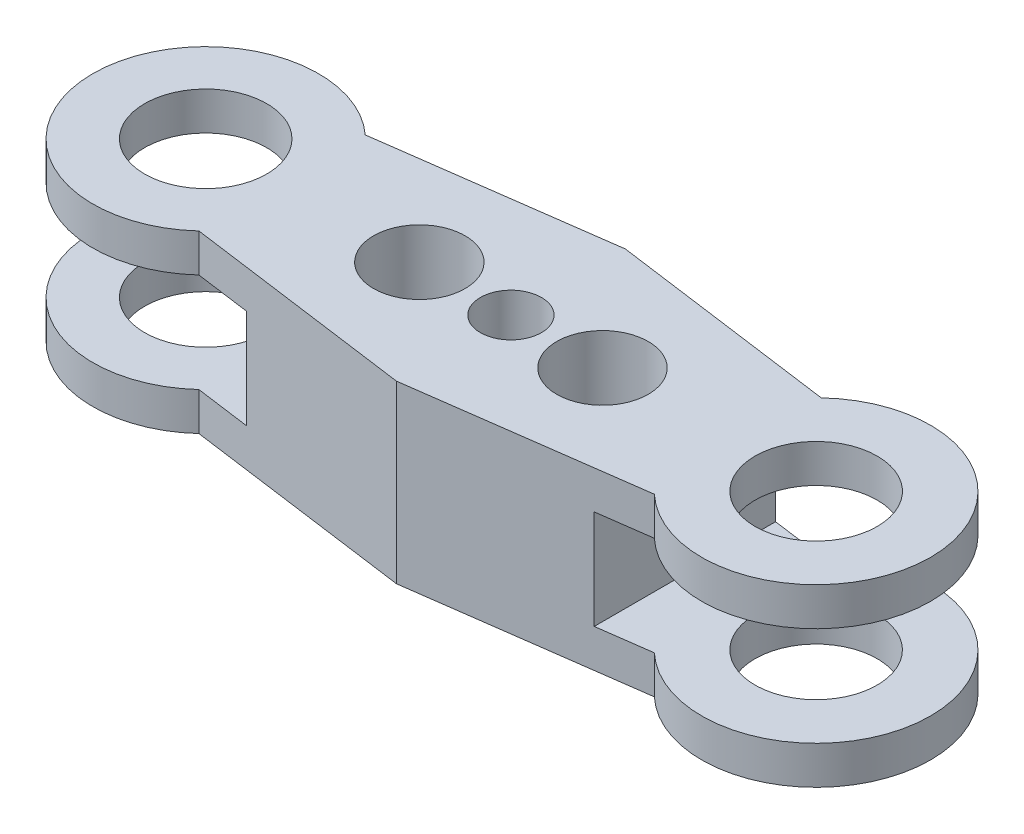
SolidWorks part; units mm, degrees
ref_plane "Ön Düzlem" through (0, 0, 0) normal (0, 0, 1) x (1, 0, 0)
ref_plane "Üst Düzlem" through (0, 0, 0) normal (0, 1, 0) x (1, 0, 0)
ref_plane "Sağ Düzlem" through (0, 0, 0) normal (1, 0, 0) x (0, 0, -1)
sketch "Çizim2" plane through (0, 0, 0) normal (0, 1, 0) x (1, 0, 0)
  line L0 (14.8663, -5.4676) -> (14.9951, -5.45)
  line L3 (14.8663, 5.4676) -> (14.9951, 5.45)
  line L4 (-14.9951, 5.45) -> (0, 7.5)
  line L5 (-14.9951, -5.45) -> (0, -7.5)
  line L6 (14.9951, 5.45) -> (0, 7.5)
  line L7 (14.9951, -5.45) -> (0, -7.5)
  arc A0 (-14.9951, 5.45) -> (-14.9951, -5.45) centre (-20, 0) ccw
  arc A1 (14.8663, -5.4676) -> (14.8663, 5.4676) centre (20, 0) ccw
  circle A2 centre (-20, 0) radius 4
  circle A3 centre (20, 0) radius 4
  circle A4 centre (-6, 0) radius 3
  circle A5 centre (6, 0) radius 3
  circle A6 centre (0, 0) radius 2
  point P4 (0, 0)
  point P10 (0, 0)
  point P15 (-14.9951, 0)
  point P20 (0, 0)
extrude "Yükseklik-Ekstrüzyon1" add sketch "Çizim2" along normal blind 11.5 contours A1 L6 L4 A0 L5 L7 A6 A5 A4 A3 A2 region at (-7.4205, 0, -5.9111)
ref_plane "Düzlem1" through (15, 0, 0) normal (1, 0, 0) x (0, 0, -1)
ref_plane "Düzlem5" through (0, 0, 0) normal (1, 0, 0) x (0, 0, -1)
sketch "Çizim14" plane through (0, 11.5, 0) normal (0, 1, 0) x (1, 0, 0)
  circle A0 centre (-20, 0) radius 4
sketch "Çizim16" plane through (0, 0, 0) normal (0, 0, 1) x (1, 0, 0)
  line L0 (-27.3994, 9) -> (-27.3994, 2.5)
  line L1 (-27.3994, 9) -> (-11.3994, 9)
  line L2 (-11.3994, 9) -> (-11.3994, 2.5)
  line L3 (-11.3994, 2.5) -> (-27.3994, 2.5)
  line L4 (-27.3994, 11.5) -> (-27.3994, 0) construction
  line L5 (-29.1019, 2.5) -> (-27.3994, 2.5)
  line L6 (-29.1019, 2.5) -> (-29.1019, 9)
  line L7 (-29.1019, 9) -> (-27.3994, 9)
  line L8 (0, -6.325) -> (0, 6.325) construction
  line L9 (29.1019, 2.5) -> (27.3994, 2.5)
  line L10 (29.1019, 9) -> (27.3994, 9)
  line L11 (29.1019, 2.5) -> (29.1019, 9)
  line L12 (11.3994, 9) -> (11.3994, 2.5)
  line L13 (11.3994, 2.5) -> (27.3994, 2.5)
  line L14 (27.3994, 9) -> (11.3994, 9)
extrude "Kes-Ekstrüzyon9" cut sketch "Çizim16" against normal blind 50 and the other way blind 50 contours L3 L2 L1 L0 | L7 L6 L5 L0 | L10 L14 L12 L13 L9 L11 region at (-19.3994, 5.75, 0) region at (-28.2507, 5.75, 0) region at (20.2507, 5.75, 0)
